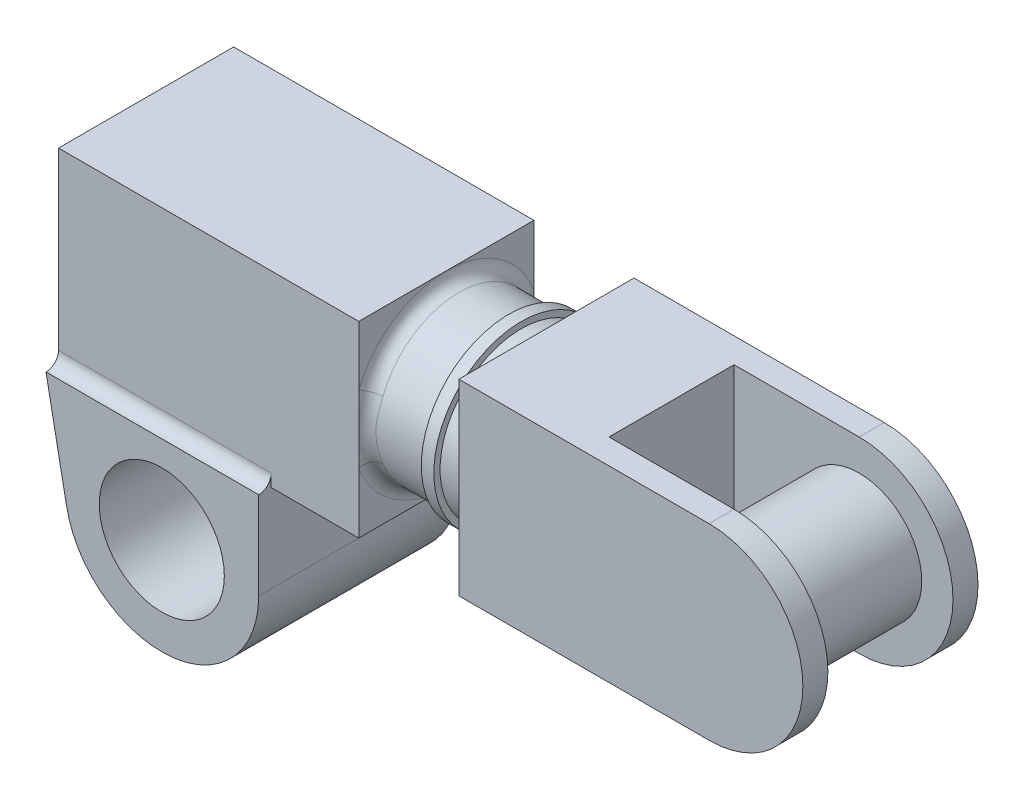
SolidWorks part; units mm, degrees
material "Aleación 6061"
ref_plane "Ön Düzlem" through (0, 0, 0) normal (0, 0, 1) x (1, 0, 0)
ref_plane "Üst Düzlem" through (0, 0, 0) normal (0, 1, 0) x (1, 0, 0)
ref_plane "Sağ Düzlem" through (0, 0, 0) normal (1, 0, 0) x (0, 0, -1)
sketch "Çizim1" plane through (0, 0, 0) normal (1, 0, 0) x (0, 0, -1)
  line L1 (-70, -75) -> (70, -75)
  line L2 (-70, -75) -> (-70, 75)
  line L3 (-70, 75) -> (70, 75)
  line L4 (70, -75) -> (70, 75)
  line L5 (-70, -75) -> (70, 75) construction
  line L6 (-70, 75) -> (70, -75) construction
  point P0 (0, 0)
  dimension "D1" = 150
  dimension "D2" = 140
extrude "Yükseklik-Ekstrüzyon1" add sketch "Çizim1" along normal blind 240
sketch "Çizim2" plane through (240, 0, 0) normal (1, 0, 0) x (0, 0, -1)
  circle A0 centre (0, 0) radius 65
  dimension "D1" = 130
extrude "Yükseklik-Ekstrüzyon2" add sketch "Çizim2" along normal blind 50
sketch "Çizim3" plane through (290, 0, 0) normal (1, 0, 0) x (0, 0, -1)
  circle A0 centre (0, 0) radius 70
  dimension "D1" = 140
extrude "Yükseklik-Ekstrüzyon3" add sketch "Çizim3" along normal blind 10
sketch "Çizim5" plane through (0, 0, 0) normal (0, 0, 1) x (1, 0, 0)
  line L0 (0, -75) -> (16.2188, -158.4383)
  line L1 (0, 75) -> (0, -75) construction
  line L2 (170.0448, -145) -> (170.0448, -75)
  line L3 (240, -75) -> (0, -75) construction
  line L4 (0, -75) -> (170.0448, -75)
  arc A0 (16.2188, -158.4383) -> (170.0448, -145) centre (92.5448, -145) ccw
  circle A1 centre (92.5448, -145) radius 50
  dimension "D1" = 155
  dimension "D2" = 100
  dimension "D3" = 191
  dimension "D4" = 85
  dimension "D5" = 70
extrude "Yükseklik-Ekstrüzyon4" add sketch "Çizim5" along normal mid plane 160
fillet "Radyus1" radius 10 3 edges at (85.0224, -75, -70) (240, 0, -65) (85.0224, -75, 70)
sketch "Çizim6" plane through (300, 0, 0) normal (1, 0, 0) x (0, 0, -1)
  circle A0 centre (0, 0) radius 65
  dimension "D1" = 130
extrude "Yükseklik-Ekstrüzyon5" add sketch "Çizim6" along normal blind 20
sketch "Çizim7" plane through (0, 0, 0) normal (0, 0, 1) x (1, 0, 0)
  line L0 (520, 75) -> (320, 75)
  line L1 (320, 75) -> (320, -75)
  line L2 (320, -75) -> (520, -75)
  line L3 (320, -65) -> (320, 65) construction
  arc A0 (520, -75) -> (520, 75) centre (520, 0) ccw
  dimension "D1" = 150
  dimension "D2" = 200
extrude "Yükseklik-Ekstrüzyon6" add sketch "Çizim7" along normal mid plane 140
sketch "Çizim8" plane through (0, 0, 0) normal (0, 0, 1) x (1, 0, 0)
  line L0 (520, 75) -> (420, 75)
  line L1 (520, 75) -> (320, 75) construction
  line L2 (420, 75) -> (420, -75)
  line L3 (320, -75) -> (520, -75) construction
  line L4 (420, -75) -> (520, -75)
  arc A0 (520, -75) -> (520, 75) centre (520, 0) ccw construction
  arc A1 (520, -75) -> (520, 75) centre (520, 0) ccw
  dimension "D1" = 100
extrude "Kes-Ekstrüzyon1" cut sketch "Çizim8" against normal mid plane 100
sketch "Çizim9" plane through (0, 0, -50) normal (0, 0, 1) x (1, 0, 0)
  circle A0 centre (520, 0) radius 50
  dimension "D1" = 100
extrude "Yükseklik-Ekstrüzyon7" add sketch "Çizim9" along normal blind 100
